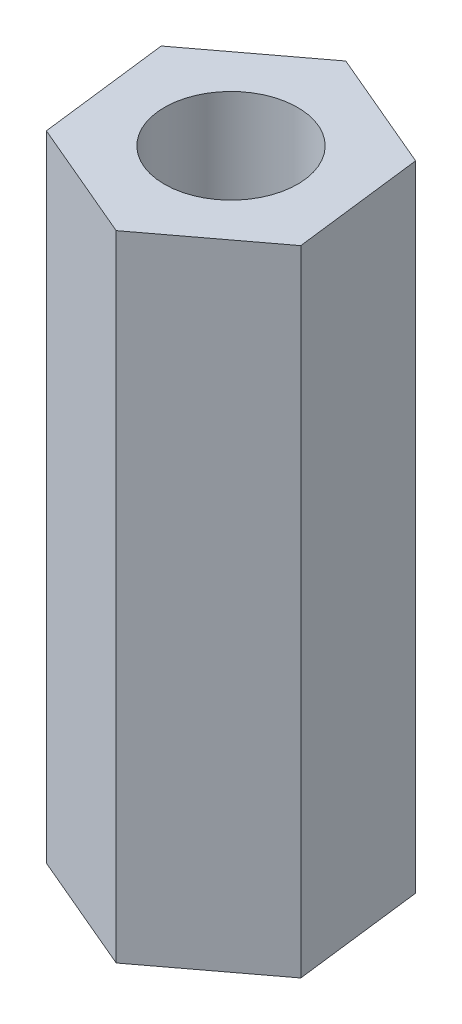
SolidWorks part; units mm, degrees
material "黄铜"
ref_plane "前视基准面" through (0, 0, 0) normal (0, 0, 1) x (1, 0, 0)
ref_plane "上视基准面" through (0, 0, 0) normal (0, 1, 0) x (1, 0, 0)
ref_plane "右视基准面" through (0, 0, 0) normal (1, 0, 0) x (0, 0, -1)
sketch "草图1" plane through (0, 0, 0) normal (0, 1, 0) x (1, 0, 0)
  line L1 (3.3206, 2.5007) -> (-0.5054, 4.1261)
  line L2 (-0.5054, 4.1261) -> (-3.826, 1.6254)
  line L3 (-3.826, 1.6254) -> (-3.3206, -2.5007)
  line L4 (-3.3206, -2.5007) -> (0.5054, -4.1261)
  line L5 (0.5054, -4.1261) -> (3.826, -1.6254)
  line L6 (3.826, -1.6254) -> (3.3206, 2.5007)
  circle A0 centre (0, 0) radius 2.1
  circle A1 centre (0, 0) radius 3.6 construction
  dimension "D1" = 4.2
  dimension "D2" = 1.5
extrude "凸台-拉伸1" add sketch "草图1" along normal blind 20
